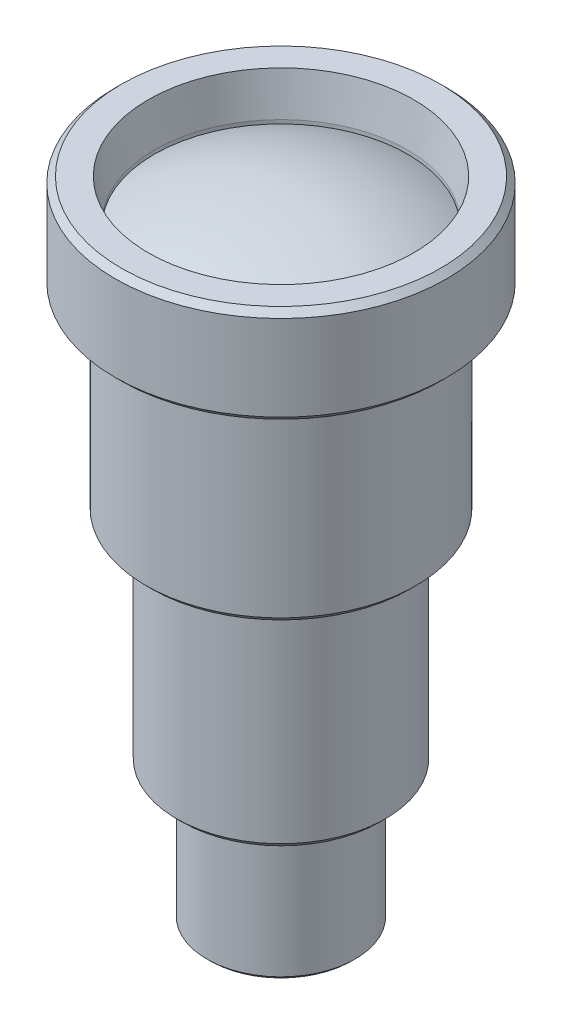
SolidWorks part; units mm, degrees
ref_plane "Front Plane" through (0, 0, 0) normal (0, 0, 1) x (1, 0, 0)
ref_plane "Top Plane" through (0, 0, 0) normal (0, 1, 0) x (1, 0, 0)
ref_plane "Right Plane" through (0, 0, 0) normal (1, 0, 0) x (0, 0, -1)
sketch "Model" plane through (0, 0, 0) normal (0, 0, 1) x (1, 0, 0)
  line L0 (49.7963, 26.2887) -> (49.7963, 25.6962)
  line L1 (49.7963, 136.7832) -> (49.7963, -125.2066) construction
  line L2 (28.5956, 131.228) -> (49.7963, 135.1361)
  line L3 (49.7963, 135.1361) -> (49.7963, 136.7832)
  line L8 (29.9931, 124.8407) -> (29.9931, 94.2978)
  line L9 (25.6108, 131.571) -> (26.6057, 131.571)
  line L10 (26.6057, 131.571) -> (26.6057, 123.8885)
  line L11 (26.6057, 123.8885) -> (27.813, 123.0409)
  line L12 (27.813, 123.0409) -> (27.813, 92.0323)
  line L27 (38.3537, 33.8239) -> (39.6448, 33.8239)
  line L28 (39.6448, 56.6844) -> (39.6448, 33.8239)
  line L29 (37.7401, 53.5094) -> (37.7401, 34.4165)
  line L53 (22.8382, 137.7526) -> (22.8382, 123.8458)
  line L54 (25.6108, 131.571) -> (25.6108, 122.8507)
  line L59 (28.5956, 131.228) -> (28.5956, 124.8407)
  line L60 (29.1882, 132.1651) -> (28.1932, 138.7478)
  line L61 (28.1932, 138.7478) -> (23.8332, 138.7478)
  line L62 (23.8332, 138.7478) -> (22.8382, 137.7526)
  line L63 (29.1882, 132.1651) -> (29.1882, 131.5554)
  line L71 (22.8382, 123.8458) -> (23.8332, 122.8507)
  line L74 (23.8332, 122.8507) -> (25.6108, 122.8507)
  line L76 (28.5956, 124.8407) -> (29.9931, 124.8407)
  line L79 (34.7762, 94.2978) -> (34.7762, 56.6844)
  line L80 (32.7863, 56.6844) -> (32.7863, 91.0374)
  line L81 (32.7863, 91.0374) -> (28.8079, 91.0374)
  line L82 (29.9931, 94.2978) -> (34.7762, 94.2978)
  line L84 (38.6499, 55.6892) -> (38.6499, 54.1017)
  line L85 (38.6499, 54.1017) -> (38.3537, 54.1017)
  line L86 (34.7762, 56.6844) -> (39.6448, 56.6844)
  line L87 (33.7812, 55.6892) -> (38.6499, 55.6892)
  line L326 (38.3537, 54.1017) -> (37.7401, 53.5094)
  line L327 (37.7401, 34.4165) -> (38.3537, 33.8239)
  line L331 (40.7241, 25.6962) -> (49.7963, 25.6962)
  line L332 (40.7241, 26.2887) -> (49.7963, 26.2887)
  line L334 (40.7241, 26.2887) -> (40.7241, 25.6962)
  line L938 (27.813, 92.0323) -> (28.8079, 91.0374)
  line L939 (32.7863, 56.6844) -> (33.7812, 55.6892)
  arc A2 (49.7963, 136.7832) -> (28.5956, 131.228) centre (49.7963, 93.5508) ccw
revolve "Revolve1" add sketch "Model" angle 360 about L1 region at (27.533, 128.0344, 0)
revolve "Revolve2" add sketch "Model<3>" angle 360 about L1 region at (40.735, 134.4748, 0)
sketch "Model<3>" plane through (0, 0, 0) normal (0, 0, 1) x (1, 0, 0) same geometry as "Model"
scale "Scale1" bodies to scale 102 103 scale about centroid uniform scaling yes scale factor 0.502986
